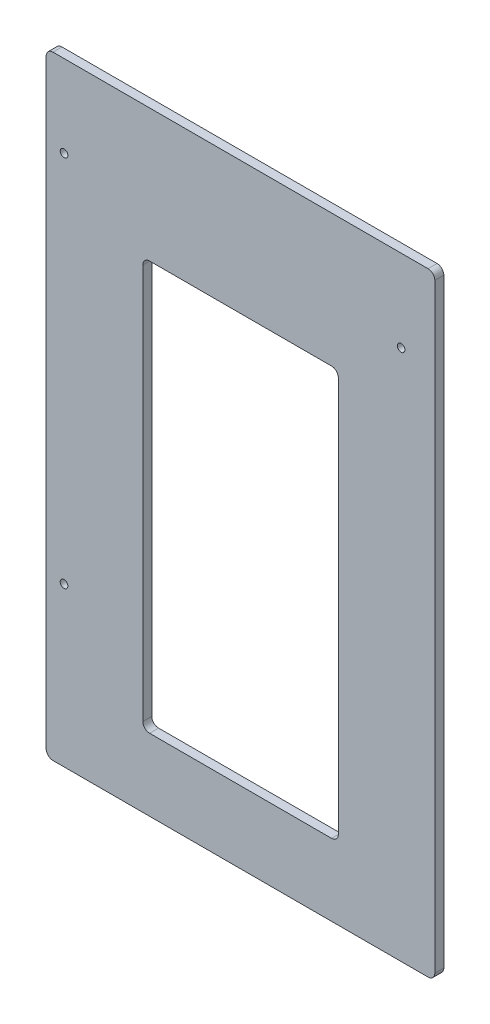
SolidWorks part; units mm, degrees
material "Verre"
ref_plane "Plan de face" through (0, 0, 0) normal (0, 0, 1) x (1, 0, 0)
ref_plane "Plan de dessus" through (0, 0, 0) normal (0, 1, 0) x (1, 0, 0)
ref_plane "Plan de droite" through (0, 0, 0) normal (1, 0, 0) x (0, 0, -1)
sketch "Esquisse1" plane through (0, 0, 0) normal (0, 0, 1) x (1, 0, 0)
  line L1 (0, 0) -> (172.93, 0)
  line L2 (0, 0) -> (0, 273)
  line L3 (0, 273) -> (172.93, 273)
  line L4 (172.93, 0) -> (172.93, 273)
  line L5 (43, 32) -> (130, 32)
  line L6 (43, 32) -> (43, 214)
  line L7 (43, 214) -> (130, 214)
  line L8 (130, 32) -> (130, 214)
  circle A0 centre (7.93, 236.5) radius 1.5
  circle A1 centre (7.93, 70.5) radius 1.5
  circle A2 centre (157.93, 236.5) radius 1.5
  dimension "D8" = 3
  dimension "D10" = 3
  dimension "D14" = 3
  dimension "D1" = 172.93
  dimension "D2" = 273
  dimension "D3" = 43
  dimension "D4" = 87
  dimension "D5" = 182
  dimension "D6" = 32
  dimension "D7" = 7.93
  dimension "D9" = 7.93
  dimension "D11" = 36.5
  dimension "D12" = 70.5
  dimension "D13" = 36.5
  dimension "D15" = 15
extrude "Boss.-Extru.1" add sketch "Esquisse1" along normal blind 4
fillet "Congé1" radius 3 8 edges at (0, 0, 2) (172.93, 0, 2) (172.93, 273, 2) (0, 273, 2) (43, 32, 2) (130, 32, 2) (130, 214, 2) (43, 214, 2)
hole_wizard "Dégagement M31" positions "Esquisse2" profile "Esquisse3" hole size "M3" standard "ISO" end condition through all
sketch "Esquisse2" plane through (0, 0, 4) normal (0, 0, 1) x (1, 0, 0)
  point P0 (7.93, 236.5)
  point P3 (7.93, 70.5)
  point P6 (157.93, 236.5)
sketch "Esquisse3" plane through (7.93, 236.5, 4) normal (1, 0, 0) x (0, -1, 0)
  line L0 (0, 0) -> (0, 4)
  line L1 (0, 4) -> (1.7, 4)
  line L2 (1.7, 4) -> (1.7, 0)
  line L5 (1.7, 0) -> (0, 0)
  line L11 (0, -6.35) -> (0, 107.95) construction
  dimension "Diamètre du perçage jusqu'au prochain" = 3.4
  dimension "Profondeur du perçage jusqu'au prochain" = 4
